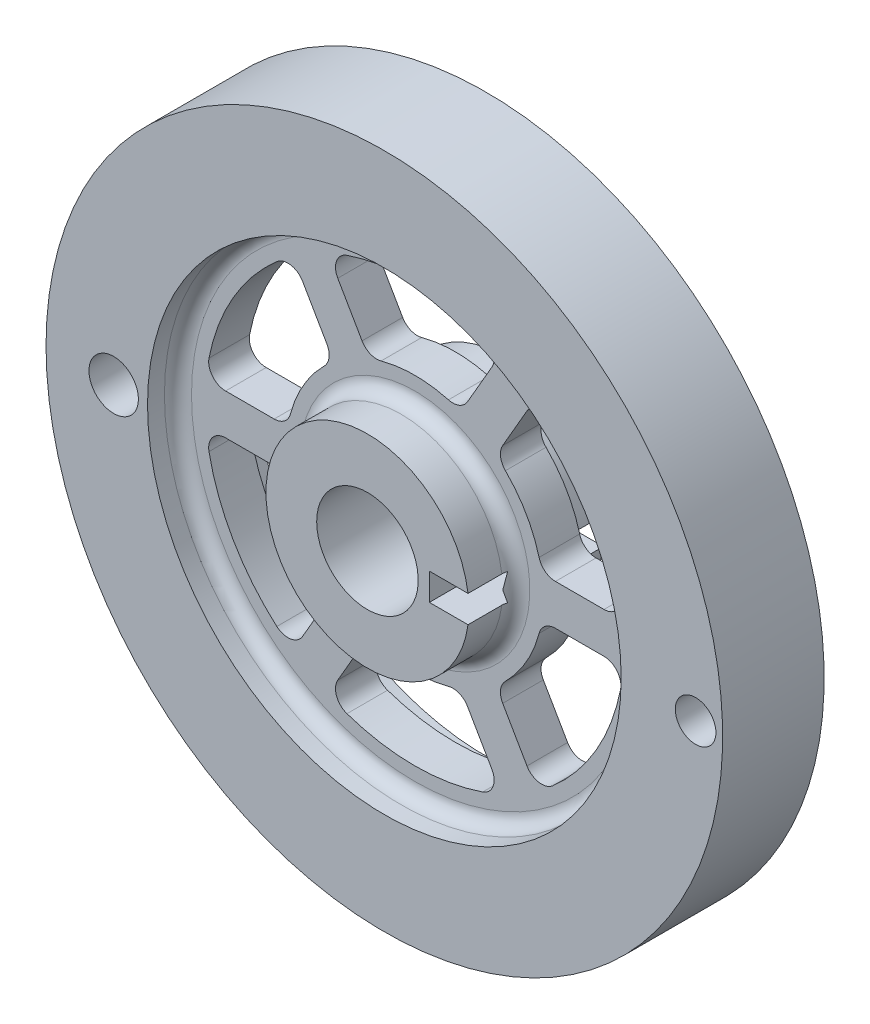
SolidWorks part; units mm, degrees
ref_plane "前视基准面" through (0, 0, 0) normal (0, 0, 1) x (1, 0, 0)
ref_plane "上视基准面" through (0, 0, 0) normal (0, 1, 0) x (1, 0, 0)
ref_plane "右视基准面" through (0, 0, 0) normal (1, 0, 0) x (0, 0, -1)
sketch "草图1" plane through (0, 0, 0) normal (0, 1, 0) x (1, 0, 0)
  line L0 (0, 20) -> (0, -20) construction
  line L1 (15, 20) -> (30, 20)
  line L2 (30, 20) -> (30, 6)
  line L3 (30, 6) -> (70, 6)
  line L4 (70, 6) -> (70, 15)
  line L5 (70, 15) -> (100, 15)
  line L6 (100, 15) -> (100, -15)
  line L7 (100, -15) -> (70, -15)
  line L8 (70, -15) -> (70, -6)
  line L9 (70, -6) -> (30, -6)
  line L10 (30, -6) -> (30, -20)
  line L11 (30, -20) -> (15, -20)
  line L12 (15, -20) -> (15, 20)
revolve "旋转1" add sketch "草图1" angle 360 about L0
fillet "圆角1" radius 4 4 edges at (-70, 0, -6) (-30, 0, -6) (-70, 0, 6) (-30, 0, 6)
ref_plane "基准面1" through (0, 0, 20) normal (0, 0, 1) x (1, 0, 0)
ref_plane "基准面2" through (0, 0, 6) normal (0, 0, 1) x (1, 0, 0)
sketch "草图4" plane through (0, 0, 0) normal (0, 0, 1) x (1, 0, 0)
  line L0 (23.9577, 29.4953) -> (36.0505, 50.4402)
  line L1 (61.709, 6) -> (37.5233, 6)
  arc A0 (37.5233, 6) -> (23.9577, 29.4953) centre (0.0052, 0.0018) ccw
  arc A1 (36.0505, 50.4402) -> (61.709, 6) centre (0.0007, -0.0013) cw
extrude "切除-拉伸3" cut sketch "草图4" against normal mid plane 12
ref_axis "基准轴1" through (0, 0, 22) along (0, 0, -1)
pattern_circular "阵列(圆周)1" count 6 over 360 about axis through (0, 0, 22) along (0, 0, -1) of "切除-拉伸3"
fillet "圆角2" radius 5 18 edges at (36.0507, -50.4416, 0) (61.7077, -6.0005, 0) (-25.6583, -56.4416, 0) (25.6572, -56.4407, 0) (23.9578, -29.4961, 0) (-61.709, -6, 0) (-36.0505, -50.4402, 0) (-13.5655, -35.4961, 0) (-36.0507, 50.4416, 0) (-61.7077, 6.0005, 0) (-37.5233, -6, 0) (25.6583, 56.4416, 0) (-25.6572, 56.4407, 0) (-23.9578, 29.4961, 0) (61.709, 6, 0) (36.0505, 50.4402, 0) (13.5655, 35.4961, 0) (37.5233, 6, 0) tangent propagation no
sketch "草图6" plane through (0, 0, 20) normal (0, 0, 1) x (1, 0, 0)
  line L0 (18.3, -4) -> (30, -4)
  line L1 (30, -4) -> (30, 4)
  line L2 (30, 4) -> (18.3, 4)
  line L3 (18.3, 4) -> (18.3, -4)
extrude "切除-拉伸6" cut sketch "草图6" against normal through all
ref_plane "基准面3" through (0, 0, 15) normal (0, 0, 1) x (1, 0, 0)
sketch "草图7" plane through (0, 0, 15) normal (0, 0, 1) x (1, 0, 0)
  circle A0 centre (92, 0) radius 6
extrude "切除-拉伸7" cut sketch "草图7" against normal through all
sketch "草图8" plane through (0, 0, 0) normal (0, 0, 1) x (1, 0, 0)
  circle A0 centre (-80, 0) radius 7.3005
extrude "切除-拉伸8" cut sketch "草图8" against normal mid plane 402
fillet "圆角3" radius 5 6 edges at (37.5225, -6.0003, 0) (13.5648, -35.4956, 0) (-23.9577, -29.4953, 0) (-37.5225, 6.0003, 0) (-13.5648, 35.4956, 0) (23.9577, 29.4953, 0) tangent propagation no
